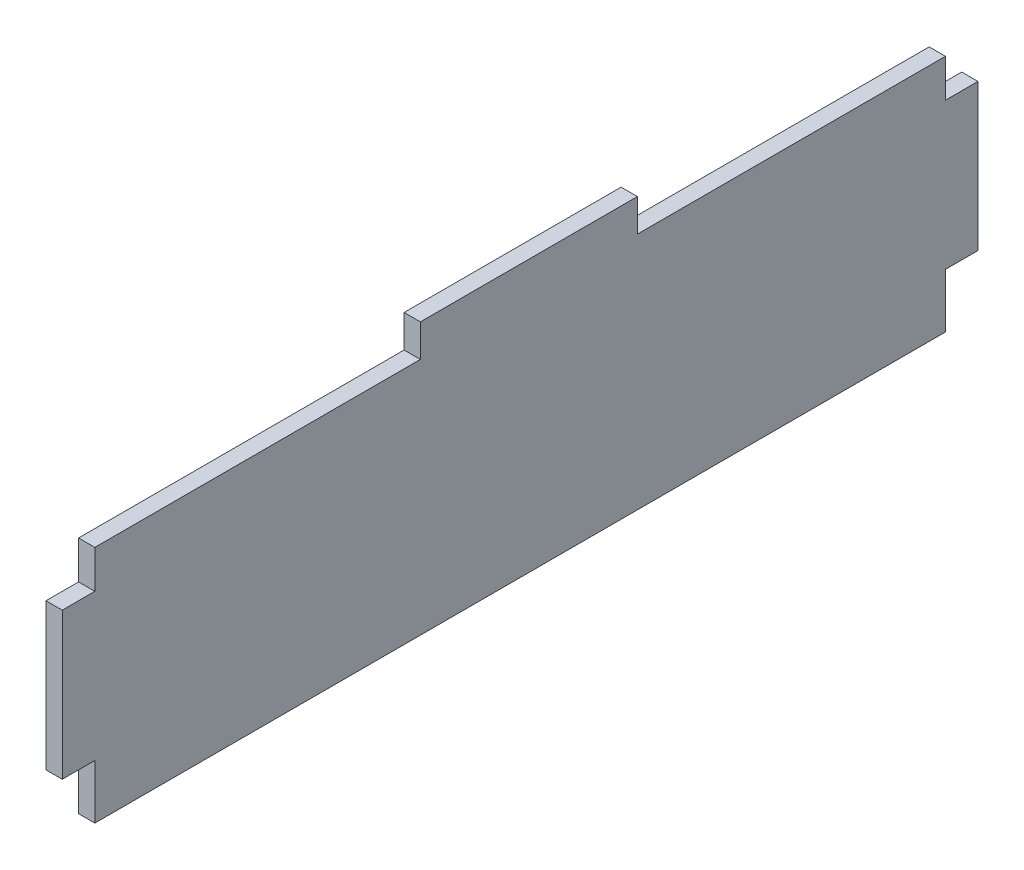
SolidWorks part; units mm, degrees
ref_plane "Front Plane" through (0, 0, 0) normal (0, 0, 1) x (1, 0, 0)
ref_plane "Top Plane" through (0, 0, 0) normal (0, 1, 0) x (1, 0, 0)
ref_plane "Right Plane" through (0, 0, 0) normal (1, 0, 0) x (0, 0, -1)
sketch "Sketch2" plane through (0, 0, 0) normal (1, 0, 0) x (0, 0, -1)
  line L1 (63, 3.0154) -> (103, 3.0154)
  line L3 (3, -47) -> (159.7817, -47)
  line L5 (-3, -10) -> (-3, -37)
  line L10 (3, -2.9846) -> (63, -2.9846)
  line L11 (63, 3.0154) -> (63, -2.9846)
  line L12 (103, 3.0154) -> (103, -2.9846)
  line L13 (165.7817, -10) -> (165.7817, -37)
  line L14 (103, -2.9846) -> (159.7817, -2.9846)
  line L16 (3, -2.9846) -> (3, -10)
  line L17 (-3, -10) -> (3, -10)
  line L18 (-3, -37) -> (3, -37)
  line L19 (3, -37) -> (3, -47)
  line L20 (159.7817, -2.9846) -> (159.7817, -10)
  line L21 (165.7817, -10) -> (159.7817, -10)
  line L22 (165.7817, -37) -> (159.7817, -37)
  line L23 (159.7817, -37) -> (159.7817, -47)
  dimension "D1" = 6
  dimension "D2" = 27
  dimension "D3" = 6
  dimension "D6" = 40
  dimension "D8" = 50.0154
  dimension "D9" = 168.7817
extrude "Boss-Extrude1" add sketch "Sketch2" along normal blind 3
